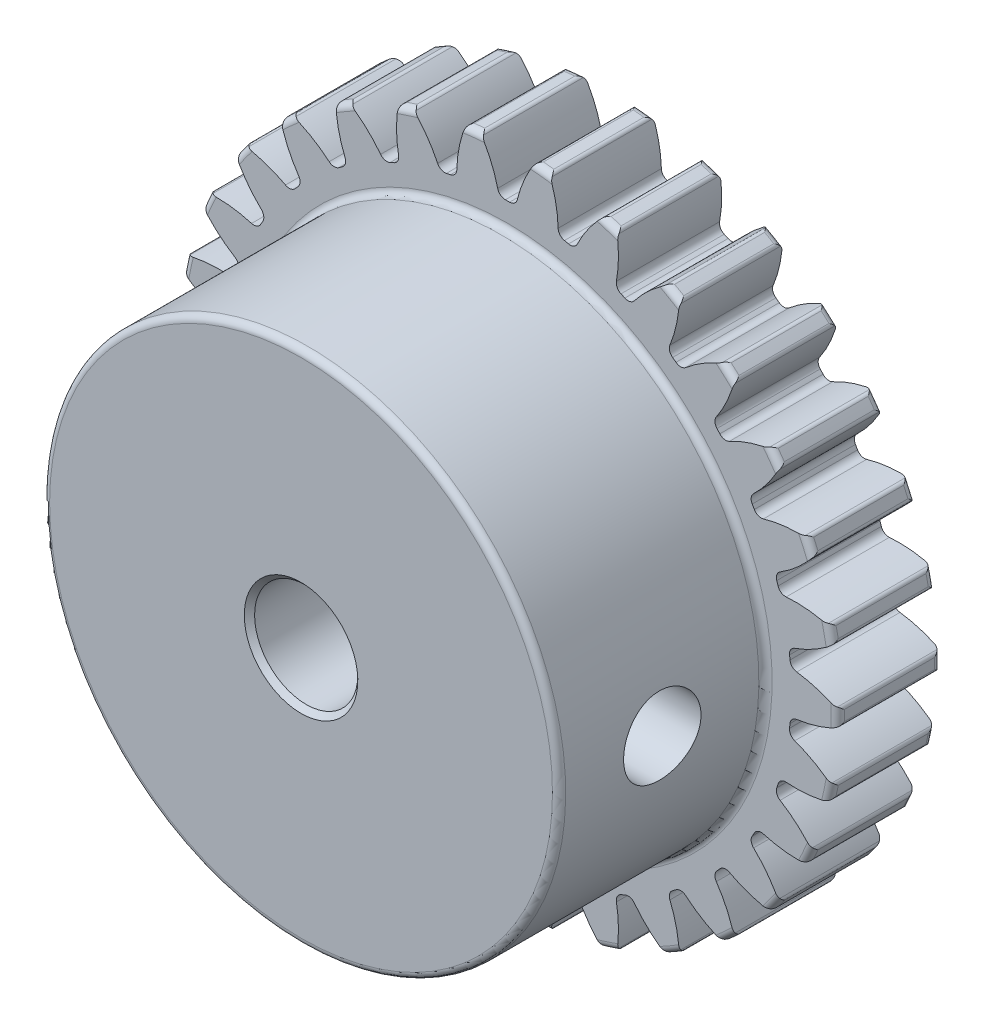
SolidWorks part; units mm, degrees
note: '?' marks a value the reader was unsure of.
ref_plane "Front Plane" through (0, 0, 0) normal (0, 0, 1) x (1, 0, 0)
ref_plane "Top Plane" through (0, 0, 0) normal (0, 1, 0) x (1, 0, 0)
ref_plane "Right Plane" through (0, 0, 0) normal (1, 0, 0) x (0, 0, -1)
sketch "Sketch1" plane through (0, 0, 0) normal (0, 0, 1) x (1, 0, 0)
  line L0 (-381, 0) -> (381, 0) construction
  line L1 (0, 0) -> (0, 2) construction
  circle A0 centre (0, 0) radius 12.8 construction
  circle A1 centre (0, 0) radius 12 construction
  circle A2 centre (0, 0) radius 11 construction
  circle A3 centre (0, 0) radius 10 construction
  circle A4 centre (0, 0) radius 2 construction
  point P9 (20.32, 0)
  dimension "D2" = 0.8
  dimension "D3" = 1.8
  dimension "D1" = 1.8
  dimension "Module" = 20.32
sketch "Sketch2" plane through (0, 0, 0) normal (1, 0, 0) x (0, 0, -1)
  line L0 (0, 0) -> (-4, 0) construction
  line L1 (-4, 0) -> (-12, 0) construction
sketch "Sketch4" plane through (0, 0, 0) normal (1, 0, 0) x (0, 0, -1)
  line L0 (-12, 2) -> (-12, 10)
  line L1 (-12, 10) -> (-4, 10)
  line L2 (-4, 10) -> (-4, 12.8)
  line L3 (-4, 12.8) -> (0, 12.8)
  line L4 (0, 12.8) -> (0, 2)
  line L5 (-4, 10) -> (-4, 0) construction
  line L6 (0, 12.8) -> (0, -12.8) construction
  line L7 (-4, 10) -> (0, 10) construction
  line L12 (-12, 2) -> (0, 2)
revolve "Revolve1" add sketch "Sketch4" angle 360 about L1
fillet "Fillet2" radius 0.256 4 edges at (0, 10, 12) (0, 10, 4) (0, 12.8, 4) (0, 12.8, 0)
sketch "Sketch7" plane through (0, 0, 4) normal (0, 0, 1) x (1, 0, 0)
  line L0 (0, 0) -> (0, 12.8) construction
  line L1 (0.628, 11.9836) -> (0.9593, 12.764) construction
  line L3 (1.338, 12.7299) -> (1.2543, 11.9343) construction
  line L4 (1.2543, 11.9343) -> (1.1498, 10.9397) construction
  line L5 (0, 0) -> (1.1498, 10.9397) construction
  line L6 (0.628, 11.9836) -> (0, 0) construction
  line L7 (0.628, 11.9836) -> (0.6699, 12.7825) construction
  line L8 (0.628, 11.9836) -> (0, 0) construction
  circle A0 centre (0, 0) radius 12.8 construction
  circle A2 centre (0, 0) radius 11 construction
  arc A3 (-0.628, 11.9836) -> (0.628, 11.9836) centre (0, 0) cw construction
  circle A4 centre (0, 0) radius 12 construction
  arc A5 (1.6314, 12.6956) -> (1.0438, 12.7574) centre (0, 0) ccw construction
  arc A6 (0.628, 11.9836) -> (1.8772, 11.8523) centre (0, 0) cw construction
  arc A7 (-1.0438, 12.7574) -> (1.0438, 12.7574) centre (0, 0) cw
  arc A8 (0.3291, 10.9951) -> (1.0438, 12.7574) centre (5.0465, 10.108) cw
  arc A9 (-0.3291, 10.9951) -> (-1.0438, 12.7574) centre (-5.0465, 10.108) ccw
  arc A10 (0.3291, 10.9951) -> (-0.3291, 10.9951) centre (0, 0) ccw
  point P26 (-0.3291, 10.9951)
  point P29 (0.3291, 10.9951)
  dimension "D5" = 4.8
  dimension "D3" = 20
  dimension "D1" = 2.5133
  dimension "D2" = 1.2566
extrude "Cut-Extrude2" cut sketch "Sketch7" against normal through all
fillet "Fillet3" radius 0.304 2 edges at (0.3291, 10.9951, 2) (-0.3291, 10.9951, 2)
fillet "Fillet4" radius 0.152 2 edges at (1.0438, 12.7574, 2) (-1.0438, 12.7574, 2)
pattern_circular "CirPattern1" count 30 over 360 about axis through (0, 0, 0) along (0, 0, 1) of "Cut-Extrude2", "Fillet3", "Fillet4"
ref_plane "Plane1" through (10, 0, 0) normal (1, 0, 0) x (0, 0, -1)
sketch "Sketch8" plane through (10, 0, 0) normal (1, 0, 0) x (0, 0, -1)
  line L3 (-12, 9.744) -> (-12, -9.744) construction
  circle A0 centre (-8, 0) radius 1.5
  dimension "Set Screw" = 3
  dimension "D1" = 4
extrude "Cut-Extrude3" cut sketch "Sketch8" against normal up to surface (10 mm away) up to plane "Right Plane"
chamfer "Chamfer1" distance 0.2 angle 45 2 edges at (0, 2, 0) (0, 2, 12)
sketch "Sketch9" [suppressed] plane through (0, 0, 0) normal (1, 0, 0) x (0, 0, -1)
  line L0 (-5.16, 6.5) -> (-11.84, 6.5) construction
  line L1 (-0.16, 7.9685) -> (-4.84, 7.9685) construction
  point P0 (-12, 6.5)
  point P1 (-5, 6.5)
  point P2 (0, 7.9685)
ref_plane "Contact Plane 1" through (0, 0, 12) normal (0, 0, 1) x (1, 0, 0)
ref_plane "Contact Plane 2" through (0, 0, 4) normal (0, 0, 1) x (1, 0, 0)
ref_plane "Contact Plane 3" through (0, 0, 0) normal (0, 0, -1) x (-1, 0, 0)
ref_axis "Center Axis 1" through (0, 0, 11.8) along (0, 0, -1)?
ref_axis "Center Axis 2" through (1.205, 0, 8) along (1, 0, 0)?
equation "\"D1@CirPattern1\"=\"Number of Teeth@Sketch1\""
equation "\"D1@Fillet2\"=\"OD@Sketch1\"*.01"
equation "\"D1@Sketch7\"=3.14159*(\"Pitch Dia.@Sketch1\"/\"Number of Teeth@Sketch1\")"
equation "\"D2@Sketch7\"=\"D1@Sketch7\"/2"
equation "\"D1@Sketch1\"=2.25mm*\"Module@Sketch1\""
equation "\"D1@Fillet3\"=.38mm*\"Module@Sketch1\""
equation "\"D1@Fillet4\"=\"D1@Fillet3\"/2"
equation "\"D5@Sketch7\"=\"Pitch Dia.@Sketch1\"/5"
equation "\"D1@Sketch8\"=(\"Overall Width@Sketch2\"-\"Face Width@Sketch2\")/2"
